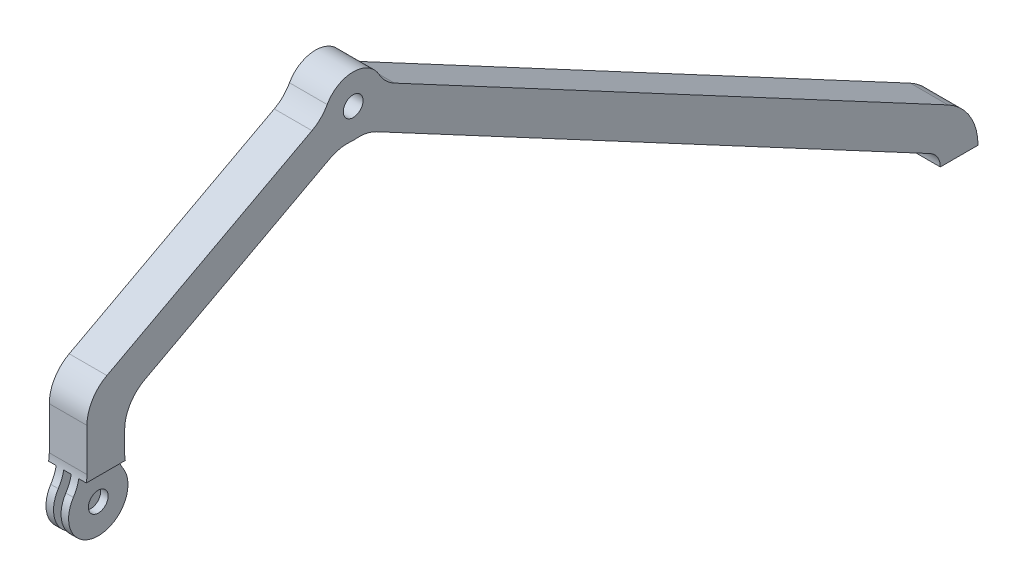
SolidWorks part; units mm, degrees
ref_plane "Front Plane" through (0, 0, 0) normal (0, 0, 1) x (1, 0, 0)
ref_plane "Top Plane" through (0, 0, 0) normal (0, 1, 0) x (1, 0, 0)
ref_plane "Right Plane" through (0, 0, 0) normal (1, 0, 0) x (0, 0, -1)
sketch "Sketch1" plane through (0, 0, 0) normal (1, 0, 0) x (0, 0, -1)
  line L0 (0, 0) -> (0, 91.4669)
  line L1 (0, 91.4669) -> (250, 225)
  line L2 (250, 225) -> (250, 91.4669) construction
  line L3 (250, 225) -> (842.3503, -91.3935)
  line L4 (862.5, -125) -> (862.5, -248.56) construction
  line L5 (250, 91.4669) -> (0, 91.4669) construction
  line L6 (250, 91.4669) -> (500, 91.4669) construction
  arc A0 (842.3503, -91.3935) -> (862.5, -125) centre (824.4, -125) cw
  dimension "D1" = 125
  dimension "D6" = 38.1
  dimension "D2" = 862.5
  dimension "D3" = 350
  dimension "D4" = 250
sketch "Sketch3" plane through (0, 0, 0) normal (0, 1, 0) x (1, 0, 0)
  line L1 (-19.05, -19.05) -> (19.05, -19.05)
  line L2 (-19.05, -19.05) -> (-19.05, 19.05)
  line L3 (-19.05, 19.05) -> (19.05, 19.05)
  line L4 (19.05, -19.05) -> (19.05, 19.05)
  line L5 (-19.05, -19.05) -> (19.05, 19.05) construction
  line L6 (-19.05, 19.05) -> (19.05, -19.05) construction
  point P0 (0, 0)
  dimension "D1" = 38.1
sweep "Sweep1" add profiles "Sketch3" path "Sketch1"
sketch "Sketch4" plane through (19.05, 0, 0) normal (1, 0, 0) x (0, 0, -1)
  line L0 (19.05, 0) -> (-19.05, 0) construction
  line L1 (250, 246.5972) -> (250, 203.4028) construction
  circle A0 centre (0, 0) radius 10
  circle A2 centre (250, 225) radius 10
  dimension "D1" = 20
  dimension "D3" = 20
extrude "Cut-Extrude1" cut sketch "Sketch4" against normal through all
sketch "Sketch5" plane through (19.05, 0, 0) normal (1, 0, 0) x (0, 0, -1)
  circle A0 centre (0, 0) radius 30
  circle A1 centre (250, 225) radius 30
  circle A3 centre (0, 0) radius 10
  circle A4 centre (250, 225) radius 10
  circle A5 centre (250, 225) radius 10 construction
  dimension "D1" = 60
  dimension "D2" = 60
extrude "Boss-Extrude1" add sketch "Sketch5" against normal up to surface (38.1 mm away)
fillet "Fillet1" radius 38.1 8 edges at (0, 80.0449, -19.05) (0, 102.8888, 19.05) (0, 23.1754, 19.05) (0, 23.1754, -19.05) (0, 197.278, -261.4669) (0, 197.278, -238.5331) (0, 230.8845, -279.4172) (0, 230.8845, -220.5828)
ref_plane "Plane1" through (0, -30, 0) normal (0, -1, 0) x (-1, 0, 0)
sketch "Sketch6" plane through (0, -30, 0) normal (0, -1, 0) x (-1, 0, 0)
  line L0 (-19.05, 30) -> (-19.05, -30) construction
  line L1 (-19.05, -43.6993) -> (19.05, -43.6993)
  line L2 (-19.05, -43.6993) -> (-19.05, 36.8419)
  line L3 (-19.05, 36.8419) -> (19.05, 36.8419)
  line L4 (19.05, -43.6993) -> (19.05, 36.8419)
  line L5 (19.05, -30) -> (19.05, 30) construction
  line L6 (-19.05, -3.4287) -> (-11.43, -3.4287) construction
  line L7 (-11.43, 36.8419) -> (-3.81, 36.8419)
  line L8 (-11.43, 36.8419) -> (-11.43, -43.6993)
  line L9 (-11.43, -43.6993) -> (-3.81, -43.6993)
  line L10 (-3.81, 36.8419) -> (-3.81, -43.6993)
  line L11 (3.81, 36.8419) -> (11.43, 36.8419)
  line L12 (3.81, 36.8419) -> (3.81, -43.6993)
  line L13 (3.81, -43.6993) -> (11.43, -43.6993)
  line L14 (11.43, 36.8419) -> (11.43, -43.6993)
  line L15 (-11.43, -3.4287) -> (-3.81, -3.4287) construction
  line L16 (-3.81, -3.4287) -> (3.81, -3.4287) construction
  line L17 (3.81, -3.4287) -> (11.43, -3.4287) construction
  line L18 (11.43, -3.4287) -> (19.05, -3.4287) construction
extrude "Cut-Extrude2" cut sketch "Sketch6" against normal blind 60 contours L8 L3 L2 L1 | L12 L3 L10 L1 | L3 L14 L1 L4 region at (15.24, -30, 3.4287) region at (0, -30, 3.4287) region at (-15.24, -30, 3.4287)
ref_point "Point1"
ref_axis "Axis1" through (0, -125, -862.5) along (0, -1, 0)
